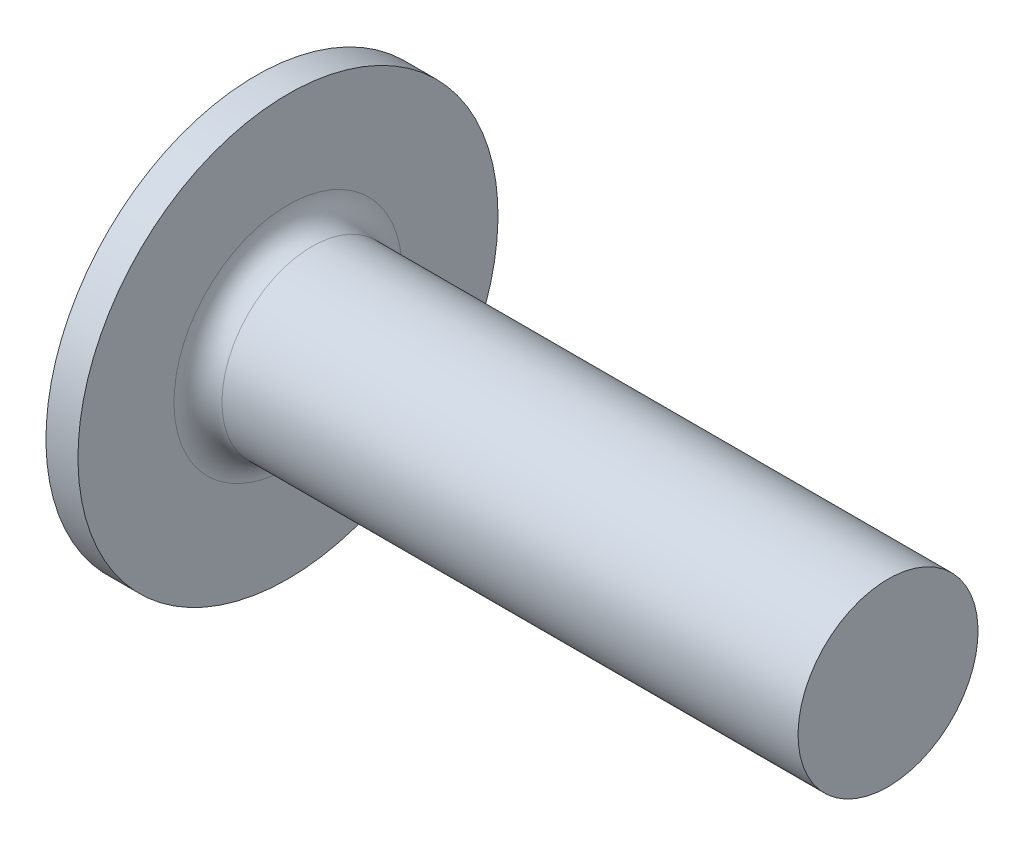
SolidWorks part; units mm, degrees
material "AISI 304"
ref_plane "Front Plane" through (0, 0, 0) normal (0, 0, 1) x (1, 0, 0)
ref_plane "Top Plane" through (0, 0, 0) normal (0, 1, 0) x (1, 0, 0)
ref_plane "Right Plane" through (0, 0, 0) normal (1, 0, 0) x (0, 0, -1)
ref_plane "Plane1" through (-0.8, 0, 0) normal (1, 0, 0) x (0, 0, -1)
sketch "Sketch1" plane through (0, 0, 0) normal (0, 0, 1) x (1, 0, 0)
  line L0 (-0.8, 0) -> (10, 0) construction
  line L1 (0, 1.5) -> (10, 1.5)
  line L2 (10, 1.5) -> (10, 0)
  line L3 (10, 0) -> (-0.8, 0)
  line L4 (-0.8, 0) -> (-0.8, 3.0381)
  line L5 (-0.8, 3.0381) -> (-0.5333, 3.5)
  line L6 (-0.5333, 3.5) -> (0, 3.5)
  line L7 (0, 3.5) -> (0, 1.5)
  dimension "M" = 3
  dimension "L" = 10
  dimension "FIX_1" = 30
  dimension "A" = 7
  dimension "E" = 0.8
  dimension "KSS_1" = 0.5333
revolve "Revolve1" add sketch "Sketch1" angle 360 about L0
cosmetic thread "Thread1" parameters "ATD"=2.459
chamfer "Chamfer1" [suppressed] distance 0.2 angle 45
sketch "Sketch2" plane through (-0.8, 0, 0) normal (1, 0, 0) x (0, 0, -1)
  line L0 (0, 0.875) -> (0, -0.875) construction
  line L1 (0.875, 0) -> (-0.875, 0) construction
  line L2 (0.7578, 0.4375) -> (-0.7578, -0.4375) construction
  line L3 (-0.7578, 0.4375) -> (0.7578, -0.4375) construction
  line L4 (0.4375, 0.7578) -> (-0.4375, -0.7578) construction
  line L5 (-0.4375, 0.7578) -> (0.4375, -0.7578) construction
  circle A0 centre (0, 0) radius 0.875 construction
  circle A1 centre (0, 0) radius 0.635 construction
  arc A2 (0.1693, 0.7443) -> (-0.1693, 0.7443) centre (0, 0.7) ccw
  arc A3 (0.7292, 0.2255) -> (0.5599, 0.5188) centre (0.6062, 0.35) ccw
  arc A4 (0.5599, -0.5188) -> (0.7292, -0.2255) centre (0.6062, -0.35) ccw
  arc A5 (-0.1693, -0.7443) -> (0.1693, -0.7443) centre (0, -0.7) ccw
  arc A6 (-0.7292, -0.2255) -> (-0.5599, -0.5188) centre (-0.6062, -0.35) ccw
  arc A7 (-0.5599, 0.5188) -> (-0.7292, 0.2255) centre (-0.6062, 0.35) ccw
  arc A8 (0.1693, 0.7443) -> (0.5599, 0.5188) centre (0.476, 0.8245) ccw
  arc A9 (0.7292, 0.2255) -> (0.7292, -0.2255) centre (0.952, 0) ccw
  arc A10 (0.5599, -0.5188) -> (0.1693, -0.7443) centre (0.476, -0.8245) ccw
  arc A11 (-0.1693, -0.7443) -> (-0.5599, -0.5188) centre (-0.476, -0.8245) ccw
  arc A12 (-0.7292, -0.2255) -> (-0.7292, 0.2255) centre (-0.952, 0) ccw
  arc A13 (-0.5599, 0.5188) -> (-0.1693, 0.7443) centre (-0.476, 0.8245) ccw
  dimension "MSM_1" = 1.75
  dimension "MSM_2" = 1.27
  dimension "MSM_3" = 0.175
  dimension "FIX_5" = 30
  dimension "FIX_6" = 30
  dimension "FIX_7" = 60
  dimension "FIX_8" = 60
extrude "Cut-Extrude1" cut sketch "Sketch2" along normal blind 0.75
fillet "Fillet1" radius 0.4 1 edges at (0, -1.5, 0)
equation "\"KSS_1@Sketch1\"= \"E@Sketch1\" * 2 / 3"
